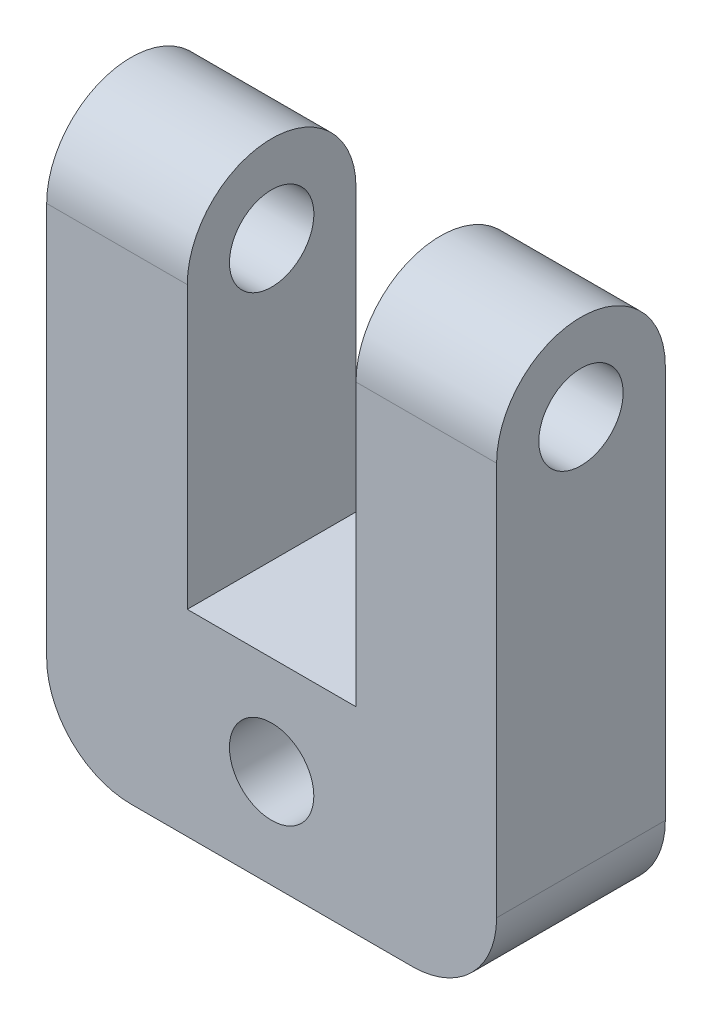
SolidWorks part; units mm, degrees
other "标注1"
sketch "草图7" plane through (20, -15, 15) normal (0.9082, -0.0936, 0.4078) x (0.1152, 0.9929, -0.0285)
other "标注2"
sketch "草图8" plane through (-10, 21.9237, 7.5) normal (-0.0355, 0.2647, 0.9637) x (0.9971, 0.0749, 0.0161)
ref_plane "前视基准面" through (0, 0, 0) normal (0, 0, 1) x (1, 0, 0)
ref_plane "上视基准面" through (0, 0, 0) normal (0, 1, 0) x (1, 0, 0)
ref_plane "右视基准面" through (0, 0, 0) normal (1, 0, 0) x (0, 0, -1)
other "Configuration Table"
sketch "草图1" plane through (0, 0, 0) normal (0, 1, 0) x (1, 0, 0)
  line L8 (-8, -3) -> (-8, 3)
  line L9 (-8, 3) -> (8, 3)
  line L10 (-8, -3) -> (8, -3)
  line L11 (8, 3) -> (8, -3)
  point P0 (0, 0)
  point P4 (0, 0)
  point P5 (-8, 0)
  point P13 (-8, 0)
extrude "凸台-拉伸1" add sketch "草图1" along normal blind 7
ref_plane "基准面1" through (0, 0, 0) normal (-1, 0, 0) x (0, 0, 1)
sketch "草图3" plane through (0, 0, 0) normal (-1, 0, 0) x (0, 0, 1)
  line L6 (3, 7) -> (-3, 7)
  line L7 (-5, 7) -> (5, 7) construction
  line L8 (-3, 7) -> (-3, 17)
  line L9 (3, 7) -> (3, 17)
  circle A1 centre (-0.0006, 16.9237) radius 1.5
  arc A2 (-3, 17) -> (3, 17) centre (0, 17) cw
  point P5 (0, 7)
  dimension "D4" = 3
extrude "凸台-拉伸2" add sketch "草图3" along normal mid plane 16
extrude "切除-拉伸2" cut sketch "草图3<2>" against normal mid plane 6
sketch "草图3<2>" plane through (0, 0, 0) normal (-1, 0, 0) x (0, 0, 1) same geometry as "草图3"
sketch3d "3D草图1"
  point P0 (2.9242, 4.2655, 5)
ref_plane "基准面2" through (0, 0, 5) normal (0, 0, 1) x (1, 0, 0)
sketch "草图9" plane through (0, 0, 5) normal (0, 0, 1) x (1, 0, 0)
  line L2 (0, 55) -> (0, -55) construction
  circle A0 centre (0, 3.5) radius 1.5
extrude "切除-拉伸3" cut sketch "草图9" against normal blind 10 contours A0
fillet "圆角4" radius 3 1 edges at (8, 0, 0) type face fillet first side face at (8, 9.25, 0) second side face at (0, 0, 0)
fillet "圆角5" radius 3 1 edges at (-8, 0, 0) type face fillet first side face at (-8, 9.25, 0) second side face at (-1.5, 0, 0)
